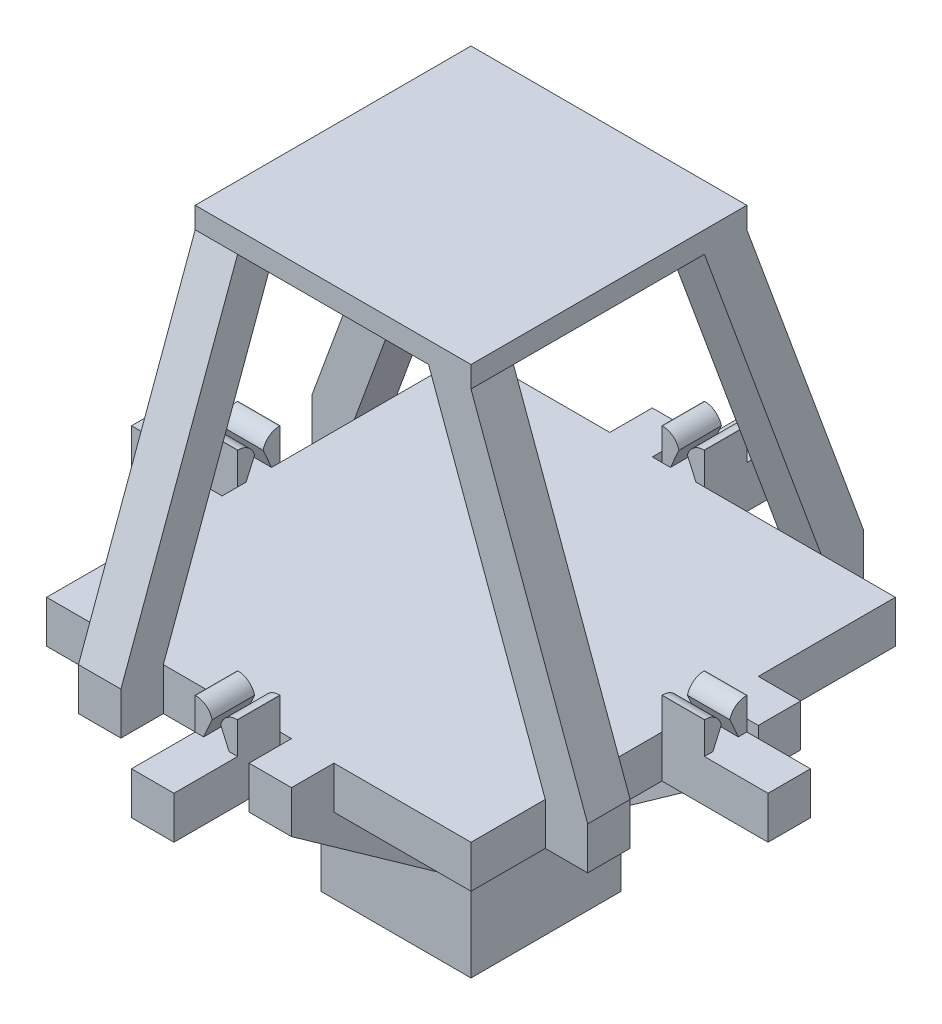
SolidWorks part; units mm, degrees
ref_plane "Front Plane" through (0, 0, 0) normal (0, 0, 1) x (1, 0, 0)
ref_plane "Top Plane" through (0, 0, 0) normal (0, 1, 0) x (1, 0, 0)
ref_plane "Right Plane" through (0, 0, 0) normal (1, 0, 0) x (0, 0, -1)
sketch "Sketch2" plane through (0, 0, 0) normal (0, 1, 0) x (1, 0, 0)
  line L1 (-50, -50) -> (50, -50)
  line L2 (-50, -50) -> (-50, 50)
  line L3 (-50, 50) -> (50, 50)
  line L4 (50, -50) -> (50, 50)
  line L5 (-50, -50) -> (50, 50) construction
  line L6 (-50, 50) -> (50, -50) construction
  point P0 (0, 0)
extrude "Boss-Extrude1" add sketch "Sketch2" along normal blind 5
sketch "Sketch3" plane through (0, 0, 0) normal (0, -1, 0) x (1, 0, 0)
  line L1 (-50, -50) -> (50, -50)
  line L2 (-50, -50) -> (-50, 50)
  line L3 (-50, 50) -> (50, 50)
  line L4 (50, -50) -> (50, 50)
  line L5 (-50, -50) -> (50, 50) construction
  line L6 (-50, 50) -> (50, -50) construction
  point P0 (0, 0)
extrude "Boss-Extrude2" add sketch "Sketch3" along normal blind 5
sketch "Sketch8" plane through (0, -5, 0) normal (0, -1, 0) x (1, 0, 0)
  circle A0 centre (0, 0) radius 5
extrude "Boss-Extrude7" add sketch "Sketch8" along normal blind 30
sketch "Sketch11" plane through (50, 0, 0) normal (1, 0, 0) x (0, 0, -1)
  line L0 (5, -5) -> (5, 12.5)
  line L3 (-5, -5) -> (5, -5)
  line L5 (5, 12.5) -> (1, 12.5)
  line L6 (1, 12.5) -> (1, 9.5)
  line L7 (-5, -5) -> (-5, 12.5)
  line L8 (-5, 12.5) -> (-1, 12.5)
  line L9 (-1, 12.5) -> (-1, 9.5)
  line L10 (-50, 5) -> (50, 5) construction
  line L11 (-1, 9.5) -> (-3, 5)
  line L12 (-3, 5) -> (3, 5)
  line L13 (3, 5) -> (1, 9.5)
  point P0 (0, 0)
  point P8 (3, 5)
  point P12 (-3, 5)
extrude "Boss-Extrude21" add sketch "Sketch11" along normal blind 10
fillet "Fillet14" radius 4 1 edges at (55, 12.5, -1)
fillet "Fillet13" radius 4 1 edges at (55, 12.5, 1)
sketch "Sketch24" plane through (60, 0, 0) normal (1, 0, 0) x (0, 0, -1)
  line L1 (-5, 5) -> (5, 5)
  line L2 (-5, 5) -> (-5, -5)
  line L3 (-5, -5) -> (5, -5)
  line L4 (5, 5) -> (5, -5)
  line L5 (-5, 5) -> (5, -5) construction
  line L6 (-5, -5) -> (5, 5) construction
  point P0 (0, 0)
extrude "Boss-Extrude22" add sketch "Sketch24" along normal blind 15
sketch "Sketch13" plane through (-50, 0, 0) normal (-1, 0, 0) x (0, 0, 1)
  line L0 (50, -5) -> (-50, -5) construction
  line L2 (-5, 12.5) -> (-5, -5)
  line L3 (-5, -5) -> (5, -5)
  line L4 (5, 12.5) -> (5, -5)
  line L5 (5, 12.5) -> (1, 12.5)
  line L6 (1, 12.5) -> (1, 9.5)
  line L7 (-5, 12.5) -> (-1, 12.5)
  line L8 (-1, 12.5) -> (-1, 9.5)
  line L9 (-1, 9.5) -> (-3, 5)
  line L10 (-3, 5) -> (3, 5)
  line L11 (3, 5) -> (1, 9.5)
  point P0 (0, 0)
  point P8 (-3, 5)
  point P13 (3, 5)
extrude "Boss-Extrude25" add sketch "Sketch13" along normal blind 10
sketch "Sketch26" plane through (-60, 0, 0) normal (-1, 0, 0) x (0, 0, 1)
  line L0 (-5, -5) -> (5, -5) construction
  line L1 (-5, 5) -> (5, 5)
  line L2 (-5, 5) -> (-5, -5)
  line L3 (-5, -5) -> (5, -5)
  line L4 (5, 5) -> (5, -5)
  line L5 (-5, 5) -> (5, -5) construction
  line L6 (-5, -5) -> (5, 5) construction
  line L7 (-5, -5) -> (5, -5) construction
  point P0 (0, 0)
extrude "Boss-Extrude26" add sketch "Sketch26" along normal blind 15
fillet "Fillet18" radius 4 1 edges at (-55, 12.5, 1)
fillet "Fillet17" radius 4 1 edges at (-55, 12.5, -1)
sketch "Sketch14" plane through (0, 0, -50) normal (0, 0, -1) x (-1, 0, 0)
  line L0 (-5, 12.5) -> (-1, 12.5)
  line L2 (-5, 12.5) -> (-5, -5)
  line L3 (-5, -5) -> (5, -5)
  line L4 (5, 12.5) -> (5, -5)
  line L5 (5, 12.5) -> (1, 12.5)
  line L6 (-1, 12.5) -> (-1, 9.5)
  line L7 (1, 12.5) -> (1, 9.5)
  line L8 (-50, 5) -> (50, 5) construction
  line L9 (-1, 9.5) -> (-3, 5)
  line L10 (-3, 5) -> (3, 5)
  line L11 (3, 5) -> (1, 9.5)
  point P0 (0, 0)
  point P11 (3, 5)
  point P12 (-3, 5)
extrude "Boss-Extrude23" add sketch "Sketch14" along normal blind 10
sketch "Sketch25" plane through (0, 0, -60) normal (0, 0, -1) x (-1, 0, 0)
  line L1 (-5, 5) -> (5, 5)
  line L2 (-5, 5) -> (-5, -5)
  line L3 (-5, -5) -> (5, -5)
  line L4 (5, 5) -> (5, -5)
  line L5 (-5, 5) -> (5, -5) construction
  line L6 (-5, -5) -> (5, 5) construction
  point P0 (0, 0)
extrude "Boss-Extrude24" add sketch "Sketch25" along normal blind 15
fillet "Fillet15" radius 4 1 edges at (-1, 12.5, -55)
fillet "Fillet16" radius 4 1 edges at (1, 12.5, -55)
sketch "Sketch12" plane through (0, 0, 50) normal (0, 0, 1) x (1, 0, 0)
  line L0 (50, -5) -> (-50, -5) construction
  line L2 (-5, 12.5) -> (-5, -5)
  line L3 (-5, -5) -> (5, -5)
  line L4 (5, 12.5) -> (5, -5)
  line L5 (5, 12.5) -> (1, 12.5)
  line L6 (1, 12.5) -> (1, 9.5)
  line L7 (-5, -5) -> (5, -5) construction
  line L8 (-5, 12.5) -> (-1, 12.5)
  line L9 (-1, 12.5) -> (-1, 9.5)
  line L10 (-1, 9.5) -> (-3, 5)
  line L11 (-3, 5) -> (3, 5)
  line L12 (3, 5) -> (1, 9.5)
  point P0 (0, 0)
  point P10 (-3, 5)
  point P15 (3, 5)
extrude "Boss-Extrude10" add sketch "Sketch12" along normal blind 10
fillet "Fillet19" radius 4 1 edges at (-1, 12.5, 55)
sketch "Sketch27" plane through (0, 0, 60) normal (0, 0, 1) x (1, 0, 0)
  line L1 (-5, 5) -> (5, 5)
  line L2 (-5, 5) -> (-5, -5)
  line L3 (-5, -5) -> (5, -5)
  line L4 (5, 5) -> (5, -5)
  line L5 (-5, 5) -> (5, -5) construction
  line L6 (-5, -5) -> (5, 5) construction
  point P0 (0, 0)
extrude "Boss-Extrude27" add sketch "Sketch27" along normal blind 15
fillet "Fillet20" radius 4 1 edges at (1, 12.5, 55)
sketch "Sketch32" plane through (0, 0, 0) normal (0, 0, 1) x (1, 0, 0)
  point P0 (0, 85)
  point P1 (-22.5, 85)
  point P2 (22.5, 85)
ref_plane "Plane1" through (0, 85, 0) normal (0, 1, 0) x (1, 0, 0)
sketch "Sketch33" plane through (0, 85, 0) normal (0, 1, 0) x (1, 0, 0)
  line L6 (32.5, -32.5) -> (32.5, 32.5)
  line L7 (32.5, 32.5) -> (-32.5, 32.5)
  line L8 (-32.5, 32.5) -> (-32.5, -32.5)
  line L9 (-32.5, -32.5) -> (32.5, -32.5)
extrude "Boss-Extrude29" add sketch "Sketch33" against normal blind 5 separate body
sketch "Sketch30" plane through (-50, 0, 0) normal (-1, 0, 0) x (0, 0, 1)
  line L0 (-50, 5) -> (-5, 5) construction
  line L1 (5, 5) -> (50, 5) construction
  line L2 (-27.5, 5) -> (-22.5, 5)
  line L3 (-27.5, 5) -> (-32.5, 5)
  line L4 (-32.5, 5) -> (-32.5, -5)
  line L5 (-5, -5) -> (-50, -5) construction
  line L6 (-32.5, -5) -> (-22.5, -5)
  line L7 (-22.5, -5) -> (-22.5, 5)
  point P0 (-27.5, 5)
  point P1 (27.5, 5)
  point P4 (-27.5, 0)
  point P7 (27.5, 0)
  point P8 (-27.5, 0)
  point P9 (-27.5, 5)
extrude "Boss-Extrude28" add sketch "Sketch30" along normal blind 10
sketch "Sketch40" plane through (0, 0, -32.5) normal (0, 0, -1) x (-1, 0, 0)
  line L0 (60, 5) -> (32.5, 80)
  line L1 (32.5, 80) -> (22.5, 80)
  line L2 (22.5, 80) -> (50, 5)
  line L3 (50, 5) -> (60, 5)
extrude "Boss-Extrude32" add sketch "Sketch40" against normal blind 10
sketch "Sketch42" plane through (50, 0, 0) normal (1, 0, 0) x (0, 0, -1)
  line L0 (-50, 5) -> (-5, 5) construction
  line L1 (-27.5, 5) -> (-22.5, 5)
  line L2 (-27.5, 5) -> (-32.5, 5)
  line L3 (-32.5, 5) -> (-32.5, -5)
  line L4 (-5, -5) -> (-50, -5) construction
  line L5 (-32.5, -5) -> (-22.5, -5)
  line L6 (-22.5, -5) -> (-22.5, 5)
  point P0 (-27.5, 5)
extrude "Boss-Extrude34" add sketch "Sketch42" along normal blind 10
sketch "Sketch43" plane through (0, 0, 32.5) normal (0, 0, 1) x (1, 0, 0)
  line L0 (32.5, 80) -> (60, 5)
  line L1 (60, 5) -> (50, 5)
  line L2 (50, 5) -> (22.5, 80)
  line L3 (-32.5, 80) -> (32.5, 80) construction
  line L4 (22.5, 80) -> (32.5, 80)
extrude "Boss-Extrude35" add sketch "Sketch43" against normal blind 10
sketch "Sketch37" plane through (0, 0, 50) normal (0, 0, 1) x (1, 0, 0)
  line L0 (-50, 5) -> (-5, 5) construction
  line L1 (-27.5, 5) -> (-22.5, 5)
  line L2 (-27.5, 5) -> (-32.5, 5)
  line L3 (-32.5, 5) -> (-32.5, -5)
  line L4 (-5, -5) -> (-50, -5) construction
  line L5 (-32.5, -5) -> (-22.5, -5)
  line L6 (-22.5, -5) -> (-22.5, 5)
  point P0 (-27.5, 5)
extrude "Boss-Extrude31" add sketch "Sketch37" along normal blind 10
sketch "Sketch41" plane through (-32.5, 0, 0) normal (-1, 0, 0) x (0, 0, 1)
  line L0 (60, 5) -> (32.5, 80)
  line L1 (32.5, 80) -> (22.5, 80)
  line L2 (-22.5, 80) -> (32.5, 80) construction
  line L3 (22.5, 80) -> (50, 5)
  line L4 (50, 5) -> (60, 5)
extrude "Boss-Extrude33" add sketch "Sketch41" against normal blind 10
sketch "Sketch44" plane through (0, 0, -50) normal (0, 0, -1) x (-1, 0, 0)
  line L0 (-50, 5) -> (-5, 5) construction
  line L1 (-27.5, 5) -> (-22.5, 5)
  line L2 (-22.5, 5) -> (-22.5, -5)
  line L3 (-5, -5) -> (-50, -5) construction
  line L4 (-22.5, -5) -> (-32.5, -5)
  line L5 (-32.5, -5) -> (-32.5, 5)
  line L6 (-32.5, 5) -> (-27.5, 5)
  point P0 (-27.5, 5)
extrude "Boss-Extrude36" add sketch "Sketch44" along normal blind 10
sketch "Sketch45" plane through (32.5, 0, 0) normal (1, 0, 0) x (0, 0, -1)
  line L0 (32.5, 80) -> (60, 5)
  line L1 (60, 5) -> (50, 5)
  line L2 (50, 5) -> (22.5, 80)
  line L3 (22.5, 80) -> (32.5, 80)
extrude "Boss-Extrude37" add sketch "Sketch45" against normal blind 10
sketch "Sketch46" plane through (0, -5, 0) normal (0, -1, 0) x (1, 0, 0)
  line L2 (-14.1361, -10.214) -> (14.1361, -10.214)
  line L3 (-14.1361, -10.214) -> (-14.1361, 10.214)
  line L4 (-14.1361, 10.214) -> (14.1361, 10.214)
  line L5 (14.1361, -10.214) -> (14.1361, 10.214)
  line L6 (-14.1361, -10.214) -> (14.1361, 10.214) construction
  line L7 (-14.1361, 10.214) -> (14.1361, -10.214) construction
  point P0 (0, 0)
extrude "Cut-Extrude1" cut sketch "Sketch46" along normal blind 30
ref_plane "Plane2" through (0, -55, 0) normal (0, -1, 0) x (-1, 0, 0)
sketch "Sketch47" plane through (0, -55, 0) normal (0, -1, 0) x (-1, 0, 0)
  line L5 (-12.7, -12.7) -> (12.7, 12.7) construction
  line L6 (-12.7, 12.7) -> (12.7, -12.7) construction
  line L7 (-17.7, 17.7) -> (17.7, 17.7)
  line L8 (-17.7, 17.7) -> (-17.7, -17.7)
  line L9 (-17.7, -17.7) -> (17.7, -17.7)
  line L10 (17.7, 17.7) -> (17.7, -17.7)
  line L11 (-17.7, 17.7) -> (17.7, -17.7) construction
  line L12 (-17.7, -17.7) -> (17.7, 17.7) construction
  point P0 (0, 0)
  point P6 (0, 0)
extrude "Boss-Extrude38" add sketch "Sketch47" against normal blind 20 separate body
sketch "Sketch49" plane through (0, -55, 0) normal (0, -1, 0) x (1, 0, 0)
  line L1 (-12.7, 12.7) -> (12.7, 12.7)
  line L2 (-12.7, 12.7) -> (-12.7, -12.7)
  line L3 (-12.7, -12.7) -> (12.7, -12.7)
  line L4 (12.7, 12.7) -> (12.7, -12.7)
  line L5 (-12.7, 12.7) -> (12.7, -12.7) construction
  line L6 (-12.7, -12.7) -> (12.7, 12.7) construction
  point P0 (0, 0)
extrude "Cut-Extrude2" cut sketch "Sketch49" against normal blind 12.7
sketch "Sketch51" plane through (0, 0, 50) normal (0, 0, 1) x (1, 0, 0)
  line L0 (17.7, 5) -> (17.7, -5)
  line L1 (5, 5) -> (50, 5) construction
  line L2 (17.7, 5) -> (7.7, 5)
  line L3 (7.7, 5) -> (7.7, -5)
  line L4 (50, -5) -> (5, -5) construction
  line L5 (17.7, -5) -> (7.7, -5)
extrude "Boss-Extrude39" add sketch "Sketch51" along normal blind 10
sketch "Sketch52" plane through (17.7, 0, 0) normal (1, 0, 0) x (0, 0, -1)
  line L0 (-60, -5) -> (-17.7, -35)
  line L1 (-17.7, -35) -> (-7.7, -35)
  line L2 (17.7, -35) -> (-17.7, -35) construction
  line L3 (-60, -5) -> (-50, -5)
  line L4 (-50, -5) -> (-7.7, -35)
extrude "Boss-Extrude40" add sketch "Sketch52" against normal blind 10
sketch "Sketch54" plane through (50, 0, 0) normal (1, 0, 0) x (0, 0, -1)
  line L0 (5, 5) -> (50, 5) construction
  line L1 (17.7, 5) -> (17.7, -5)
  line L2 (50, -5) -> (5, -5) construction
  line L3 (17.7, -5) -> (7.7, -5)
  line L4 (7.7, -5) -> (7.7, 5)
  line L5 (7.7, 5) -> (17.7, 5)
  point P0 (17.7, 5)
extrude "Boss-Extrude41" add sketch "Sketch54" along normal blind 10
sketch "Sketch55" plane through (0, 0, -17.7) normal (0, 0, -1) x (-1, 0, 0)
  line L0 (-60, -5) -> (-17.7, -35)
  line L1 (-17.7, -35) -> (-7.7, -35)
  line L2 (17.7, -35) -> (-17.7, -35) construction
  line L3 (-7.7, -35) -> (-17.7, -35) construction
  line L4 (-7.7, -35) -> (-50, -5)
  line L5 (-50, -5) -> (-60, -5)
extrude "Boss-Extrude42" add sketch "Sketch55" against normal blind 10
sketch "Sketch56" plane through (0, 0, -50) normal (0, 0, -1) x (-1, 0, 0)
  line L0 (5, 5) -> (50, 5) construction
  line L1 (17.2831, 5) -> (7.2831, 5)
  line L2 (7.2831, 5) -> (7.2831, -5)
  line L3 (50, -5) -> (5, -5) construction
  line L4 (7.2831, -5) -> (17.2831, -5)
  line L5 (17.2831, -5) -> (17.2831, 5)
  point P0 (17.2831, 5)
extrude "Boss-Extrude43" add sketch "Sketch56" along normal blind 10
sketch "Sketch58" plane through (-17.2831, 0, 0) normal (-1, 0, 0) x (0, 0, 1)
  line L0 (-60, -5) -> (-17.7, -35)
  line L1 (-17.7, -35) -> (-7.7, -35)
  line L2 (-7.7, -35) -> (-50, -5)
  line L3 (-50, -5) -> (-60, -5)
extrude "Boss-Extrude47" add sketch "Sketch58" against normal blind 10
sketch "Sketch59" plane through (-50, 0, 0) normal (-1, 0, 0) x (0, 0, 1)
  line L0 (5, 5) -> (50, 5) construction
  line L1 (18.6556, 5) -> (8.6556, 5)
  line L2 (8.6556, 5) -> (8.6556, -5)
  line L3 (50, -5) -> (5, -5) construction
  line L4 (8.6556, -5) -> (18.6556, -5)
  line L5 (18.6556, -5) -> (18.6556, 5)
  point P0 (18.6556, 5)
extrude "Boss-Extrude48" add sketch "Sketch59" along normal blind 10
sketch "Sketch61" plane through (0, 0, 18.6556) normal (0, 0, 1) x (1, 0, 0)
  line L0 (-60, -5) -> (-17.7, -35)
  line L1 (-17.7, -35) -> (-7.7, -35)
  line L2 (7.7, -35) -> (-17.7, -35) construction
  line L3 (-50, -5) -> (-7.7, -35)
  line L4 (-50, -5) -> (-60, -5)
extrude "Boss-Extrude52" add sketch "Sketch61" against normal blind 10
